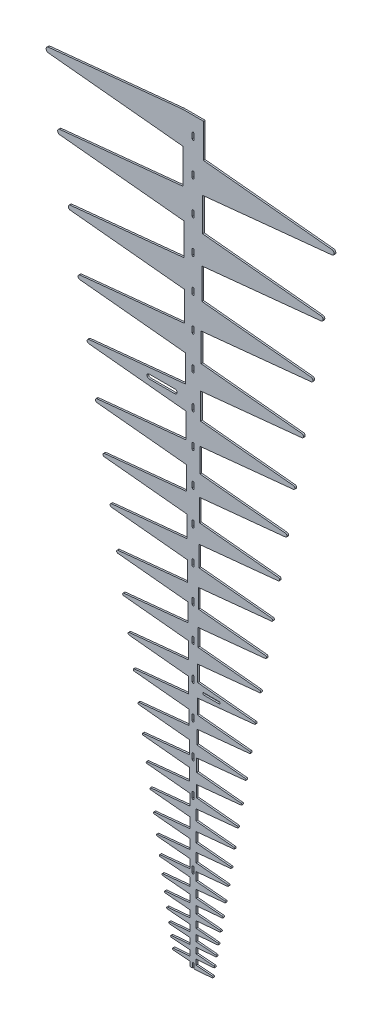
SolidWorks part; units mm, degrees
material "Copper"
ref_plane "front" through (0, 0, 0) normal (0, 0, 1) x (1, 0, 0)
ref_plane "top" through (0, 0, 0) normal (0, 1, 0) x (1, 0, 0)
ref_plane "right" through (0, 0, 0) normal (1, 0, 0) x (0, 0, -1)
ref_axis "Axis1" through (0, -2.7284, 0) along (0, 1, 0)
sketch "Sketch5" plane through (0, 0, 0) normal (0, 0, 1) x (1, 0, 0)
  line L1 (0.4572, 17.3748) -> (0.4572, 16.7446) construction
  line L2 (0.819, 67.0336) -> (11.8645, 68.1402)
  line L4 (11.8645, 68.5446) -> (0.8887, 69.6408)
  line L5 (-0.444, 34.8013) -> (-5.904, 34.2717)
  line L6 (0.4572, 34.8888) -> (6.1549, 35.4415)
  line L7 (6.155, 35.6943) -> (0.4625, 36.2508)
  line L8 (-6.4164, 37.1761) -> (-0.4818, 37.7606)
  line L9 (6.6886, 38.7197) -> (0.5018, 39.3334)
  line L10 (-6.9722, 40.3276) -> (-0.5227, 40.9717)
  line L11 (7.2676, 42.0024) -> (0.5445, 42.6782)
  line L12 (0.5445, 44.5635) -> (0.5445, 42.6782)
  line L13 (-0.5227, 42.7855) -> (-0.5227, 40.9717)
  line L14 (-0.444, 36.3394) -> (-6.4163, 36.9233)
  line L15 (-0.5227, 42.7855) -> (-7.5753, 43.4944)
  line L16 (-5.9039, 34.0189) -> (-0.4572, 33.4948)
  line L17 (0.5018, 41.074) -> (7.2675, 41.7497)
  line L18 (-0.4818, 39.431) -> (-0.4818, 37.7606)
  line L19 (0.4625, 37.8536) -> (0.4625, 36.2508)
  line L20 (-0.444, 36.3394) -> (-0.444, 34.8013)
  line L21 (0.5018, 41.074) -> (0.5018, 39.3334)
  line L22 (-0.6677, 54.647) -> (-9.6631, 55.5487)
  line L23 (-9.663, 55.9026) -> (-0.7246, 56.7938)
  line L24 (0.8887, 69.6408) -> (0.8887, 72.7352)
  line L25 (-0.853, 69.8147) -> (-0.853, 66.8661)
  line L26 (0.4625, 37.8536) -> (6.6885, 38.4669)
  line L27 (-0.4818, 39.431) -> (-6.9721, 40.0748)
  line L28 (-0.853, 69.8147) -> (-12.3433, 70.9623)
  line L29 (-12.3432, 71.4172) -> (-0.9257, 72.5545)
  line L30 (-7.5753, 43.7471) -> (-0.5671, 44.4517)
  line L31 (-0.5671, 44.4517) -> (-0.5671, 46.4176)
  line L32 (-0.5671, 46.4176) -> (-8.2061, 47.1795)
  line L33 (-8.2061, 47.4828) -> (-0.6155, 48.2385)
  line L35 (-0.6155, 48.2385) -> (-0.6155, 50.3737)
  line L36 (-0.6155, 50.3737) -> (-8.9161, 51.2055)
  line L37 (-8.9162, 51.5088) -> (-0.6677, 52.3407)
  line L38 (-0.6677, 52.3407) -> (-0.6677, 54.647)
  line L39 (0.5445, 44.5635) -> (7.8864, 45.3016)
  line L40 (7.8863, 45.5746) -> (0.5908, 46.3022)
  line L41 (0.5908, 46.3022) -> (0.5908, 48.3586)
  line L42 (0.5908, 48.3586) -> (8.5538, 49.1514)
  line L43 (8.5539, 49.4547) -> (0.6411, 50.2477)
  line L44 (0.6411, 50.2477) -> (0.6411, 52.4726)
  line L45 (0.6411, 52.4726) -> (9.2935, 53.3452)
  line L46 (9.2934, 53.6485) -> (0.6956, 54.5104)
  line L47 (0.6956, 56.9354) -> (10.0724, 57.8704)
  line L48 (10.0725, 58.2242) -> (0.7547, 59.1594)
  line L49 (0.6956, 54.5104) -> (0.6956, 56.9354)
  line L50 (-0.7246, 56.7938) -> (-0.7246, 59.3079)
  line L51 (-0.7246, 59.3079) -> (-10.499, 60.2888)
  line L52 (-10.4989, 60.6426) -> (-0.7862, 61.6131)
  line L53 (-0.7862, 61.6131) -> (-0.7862, 64.3522)
  line L54 (0.7547, 59.1594) -> (0.7547, 61.767)
  line L55 (0.7547, 61.767) -> (10.9198, 62.7827)
  line L56 (10.9197, 63.1871) -> (0.819, 64.1924)
  line L57 (0.819, 64.1924) -> (0.819, 67.0336)
  line L58 (-2.6379, 14.96) -> (-23.301, 132.1467) construction
  line L59 (-1.6146, 132.1467) -> (-0.1828, 14.96) construction
  line L60 (-0.7862, 64.3522) -> (-11.3824, 65.4068)
  line L61 (-11.3826, 65.8112) -> (-0.853, 66.8661)
  line L62 (-0.9257, 72.5545) -> (-0.9257, 75.766)
  line L63 (0.8887, 72.7352) -> (12.8662, 73.9282)
  line L64 (12.8663, 74.3832) -> (0.9641, 75.5765)
  line L65 (0.9641, 75.5765) -> (0.9641, 78.9109)
  line L66 (-0.9257, 75.766) -> (-13.4111, 77.0178)
  line L67 (-13.411, 77.4727) -> (-1.0044, 78.714)
  line L68 (-1.0044, 78.714) -> (-1.0044, 82.2104)
  line L69 (-1.0044, 82.2104) -> (-14.5463, 83.563)
  line L70 (0.9641, 78.9109) -> (13.9552, 80.2107)
  line L71 (13.9552, 80.7162) -> (1.0463, 82.0056)
  line L72 (1.0463, 82.0056) -> (1.0463, 85.636)
  line L73 (-14.5465, 84.0685) -> (-1.0897, 85.4213)
  line L74 (-1.0897, 85.4213) -> (-1.0897, 89.1922)
  line L75 (1.0463, 85.636) -> (15.1622, 87.055)
  line L76 (15.1622, 87.5605) -> (1.1353, 88.9688)
  line L77 (1.1353, 88.9688) -> (1.1353, 92.9201)
  line L78 (-1.0897, 89.1922) -> (-15.7803, 90.6672)
  line L79 (-15.7803, 91.2232) -> (-1.1824, 92.6876)
  line L80 (-1.1824, 92.6876) -> (-1.1824, 96.7798)
  line L81 (1.1353, 92.9201) -> (16.4484, 94.4562)
  line L82 (16.4484, 95.0122) -> (1.2319, 96.5378)
  line L83 (1.2319, 96.5378) -> (1.2319, 100.8239)
  line L84 (-1.1824, 96.7798) -> (-17.121, 98.3778)
  line L85 (-17.121, 98.9844) -> (-1.283, 100.5718)
  line L86 (-1.283, 100.5718) -> (-1.283, 105.013)
  line L87 (1.2319, 100.8239) -> (17.846, 102.4891)
  line L88 (17.846, 103.0957) -> (1.3366, 104.7504)
  line L89 (0, 0) -> (0, 132.1467) construction
  line L90 (1.3366, 104.7504) -> (1.3366, 109.4001)
  line L91 (1.6146, 132.1467) -> (0.1828, 14.96) construction
  line L92 (2.6379, 14.96) -> (23.301, 132.1467) construction
  line L93 (-1.283, 105.013) -> (-18.5778, 106.7464)
  line L95 (-18.5779, 107.4035) -> (-1.3922, 109.1265)
  line L96 (-1.3922, 109.1265) -> (-1.3922, 113.9465)
  line L97 (1.3366, 109.4001) -> (19.3644, 111.2074)
  line L98 (19.3645, 111.8645) -> (1.4503, 113.6614)
  line L99 (1.4503, 113.6614) -> (1.4503, 118.7058)
  line L100 (-1.3922, 113.9465) -> (-20.1606, 115.829)
  line L101 (-20.1606, 116.5367) -> (-1.5106, 118.4086)
  line L102 (-1.5106, 118.4086) -> (-1.5106, 123.64)
  line L103 (1.4503, 118.7058) -> (21.0141, 120.6695)
  line L104 (21.0141, 121.3771) -> (1.5697, 123.3306)
  line L105 (-1.5106, 123.64) -> (-21.88, 125.6864)
  line L106 (-21.8797, 126.4446) -> (-1.5697, 128.4732)
  line L107 (-0.4572, 33.4948) -> (-0.4572, 32.0694)
  line L108 (-1.5697, 128.4732) -> (1.5697, 128.4732)
  line L109 (1.5697, 128.4732) -> (1.5697, 123.3306)
  line L110 (0.4572, 34.8888) -> (0.4572, 33.4069)
  line L111 (0.4572, 33.4069) -> (5.6631, 32.906)
  line L112 (5.663, 32.6532) -> (0.4572, 32.1566)
  line L113 (0.4572, 32.1566) -> (0.4572, 30.7855)
  line L114 (-0.4572, 32.0694) -> (-5.4319, 31.595)
  line L115 (-5.4317, 31.3421) -> (-0.4572, 30.8719)
  line L116 (-0.4572, 30.8719) -> (-0.4572, 29.553)
  line L117 (0.4572, 30.7855) -> (5.2098, 30.3364)
  line L118 (5.2097, 30.0835) -> (0.4572, 29.6386)
  line L119 (0.4572, 29.6386) -> (0.4572, 28.3698)
  line L120 (-0.4572, 29.553) -> (-4.9966, 29.1281)
  line L121 (-4.9965, 28.8752) -> (-0.4572, 28.4545)
  line L122 (-0.4572, 28.4545) -> (-0.4572, 27.234)
  line L123 (-0.4572, 27.234) -> (-4.5955, 26.8546)
  line L124 (0.4572, 28.3698) -> (4.792, 27.9681)
  line L125 (4.7919, 27.7152) -> (0.4572, 27.3178)
  line L126 (0.4572, 27.3178) -> (0.4572, 26.1436)
  line L127 (-4.5954, 26.6016) -> (-0.4572, 26.2265)
  line L128 (-0.4572, 26.2265) -> (-0.4572, 25.0969)
  line L129 (-0.4572, 25.0969) -> (-4.2258, 24.7593)
  line L130 (0.4572, 26.1436) -> (4.4069, 25.7856)
  line L131 (4.4068, 25.5326) -> (0.4572, 25.1788)
  line L132 (0.4572, 25.1788) -> (0.4572, 24.0921)
  line L133 (-4.2257, 24.5063) -> (-0.4572, 24.173)
  line L134 (-0.4572, 24.173) -> (-0.4572, 23.1275)
  line L135 (0.4572, 24.0921) -> (4.0519, 23.7741)
  line L136 (4.0518, 23.5211) -> (0.4572, 23.2073)
  line L137 (0.4572, 23.2073) -> (0.4572, 22.2016)
  line L138 (-0.4572, 23.1275) -> (-3.885, 22.8283)
  line L139 (-3.8849, 22.5753) -> (-0.4572, 22.2803)
  line L140 (-0.4572, 22.2803) -> (-0.4572, 21.3127)
  line L141 (0.4572, 22.2016) -> (3.7248, 21.9203)
  line L142 (3.7246, 21.6673) -> (0.4572, 21.3902)
  line L143 (0.4572, 21.3902) -> (0.4572, 20.4594)
  line L144 (-0.4572, 21.3127) -> (-3.5709, 21.0487)
  line L145 (-3.5707, 20.7956) -> (-0.4572, 20.5357)
  line L146 (-0.4572, 20.5357) -> (-0.4572, 19.6403)
  line L147 (0.4572, 20.4594) -> (3.4232, 20.2119)
  line L148 (3.423, 19.9588) -> (0.4572, 19.7154)
  line L149 (0.4572, 19.7154) -> (0.4572, 18.8541)
  line L150 (-0.4572, 19.6403) -> (-3.2814, 19.4086)
  line L151 (-3.2812, 19.1554) -> (-0.4572, 18.9278)
  line L152 (-0.4572, 18.9278) -> (-0.4572, 18.0993)
  line L153 (0.4572, 18.8541) -> (3.1452, 18.6374)
  line L154 (3.145, 18.3842) -> (0.4572, 18.1716)
  line L155 (0.4572, 18.1716) -> (0.4572, 17.3748)
  line L156 (-0.4572, 18.0993) -> (-3.0145, 17.897)
  line L157 (-3.0143, 17.6438) -> (-0.4572, 17.4456)
  line L158 (-0.4572, 17.4456) -> (-0.4572, 16.8716)
  line L159 (0.4572, 17.3748) -> (2.8889, 17.1863)
  line L160 (2.8889, 16.9331) -> (0.4572, 16.7446)
  line L162 (-7.4216, 17.399) -> (-1.0806, 17.399) construction
  line L163 (11.7994, 111.536) -> (-7.7641, 111.536) construction
  line L164 (0.4572, 16.7446) -> (0.127, 16.7446)
  line L165 (0.127, 16.7446) -> (0.127, 17.3965)
  line L166 (-0.127, 17.3965) -> (-0.127, 16.7446)
  line L167 (-0.127, 16.7446) -> (-0.3302, 16.7446)
  arc A0 (6.1549, 35.4415) -> (6.155, 35.6943) centre (6.1426, 35.5679) ccw
  arc A1 (-6.4163, 36.9233) -> (-6.4164, 37.1761) centre (-6.4039, 37.0497) cw
  arc A2 (6.6885, 38.4669) -> (6.6886, 38.7197) centre (6.6761, 38.5933) ccw
  arc A3 (-6.9721, 40.0748) -> (-6.9722, 40.3276) centre (-6.9596, 40.2012) cw
  arc A4 (7.2675, 41.7497) -> (7.2676, 42.0024) centre (7.2549, 41.8761) ccw
  arc A5 (-9.6631, 55.5487) -> (-9.663, 55.9026) centre (-9.6454, 55.7257) cw
  arc A6 (10.0724, 57.8704) -> (10.0725, 58.2242) centre (10.0548, 58.0473) ccw
  arc A7 (10.9198, 62.7827) -> (10.9197, 63.1871) centre (10.8996, 62.9849) ccw
  arc A8 (11.8645, 68.1402) -> (11.8645, 68.5446) centre (11.8443, 68.3424) ccw
  arc A9 (-10.499, 60.2888) -> (-10.4989, 60.6426) centre (-10.4812, 60.4657) cw
  arc A10 (-11.3824, 65.4068) -> (-11.3826, 65.8112) centre (-11.3623, 65.609) cw
  arc A11 (-12.3433, 70.9623) -> (-12.3432, 71.4172) centre (-12.3205, 71.1898) cw
  arc A12 (12.8662, 73.9282) -> (12.8663, 74.3832) centre (12.8435, 74.1557) ccw
  arc A13 (-13.4111, 77.0178) -> (-13.411, 77.4727) centre (-13.3883, 77.2452) cw
  arc A14 (13.9552, 80.2107) -> (13.9552, 80.7162) centre (13.93, 80.4634) ccw
  circle A15 centre (-2.6379, 35.7196) radius 0.539 construction
  circle A16 centre (-3.8606, 58.0473) radius 0.871 construction
  arc A17 (-14.5463, 83.563) -> (-14.5465, 84.0685) centre (-14.5211, 83.8158) cw
  arc A18 (15.1622, 87.055) -> (15.1622, 87.5605) centre (15.1368, 87.3077) ccw
  arc A19 (-7.5753, 43.4944) -> (-7.5753, 43.7471) centre (-7.5626, 43.6207) cw
  arc A20 (-8.2061, 47.1795) -> (-8.2061, 47.4828) centre (-8.191, 47.3311) cw
  arc A21 (-8.9161, 51.2055) -> (-8.9162, 51.5088) centre (-8.9009, 51.3572) cw
  arc A22 (7.8864, 45.3016) -> (7.8863, 45.5746) centre (7.8727, 45.4381) ccw
  arc A23 (8.5538, 49.1514) -> (8.5539, 49.4547) centre (8.5387, 49.3031) ccw
  arc A24 (9.2935, 53.3452) -> (9.2934, 53.6485) centre (9.2782, 53.4968) ccw
  arc A25 (-15.7803, 90.6672) -> (-15.7803, 91.2232) centre (-15.7524, 90.9452) cw
  arc A26 (16.4484, 94.4562) -> (16.4484, 95.0122) centre (16.4205, 94.7342) ccw
  arc A27 (-17.121, 98.3778) -> (-17.121, 98.9844) centre (-17.0906, 98.6811) cw
  arc A28 (17.846, 102.4891) -> (17.846, 103.0957) centre (17.8156, 102.7924) ccw
  arc A29 (-18.5778, 106.7464) -> (-18.5779, 107.4035) centre (-18.5449, 107.075) cw
  arc A30 (19.3644, 111.2074) -> (19.3645, 111.8645) centre (19.3315, 111.536) ccw
  arc A31 (-20.1606, 115.829) -> (-20.1606, 116.5367) centre (-20.1251, 116.1829) cw
  arc A32 (21.0141, 120.6695) -> (21.0141, 121.3771) centre (20.9786, 121.0233) ccw
  arc A33 (-21.88, 125.6864) -> (-21.8797, 126.4446) centre (-21.8419, 126.0655) cw
  arc A34 (-5.904, 34.2717) -> (-5.9039, 34.0189) centre (-5.8918, 34.1453) ccw
  arc A35 (5.6631, 32.906) -> (5.663, 32.6532) centre (5.651, 32.7796) cw
  arc A36 (-5.4319, 31.595) -> (-5.4317, 31.3421) centre (-5.4198, 31.4685) ccw
  arc A37 (5.2098, 30.3364) -> (5.2097, 30.0835) centre (5.1979, 30.2099) cw
  arc A38 (-4.9966, 29.1281) -> (-4.9965, 28.8752) centre (-4.9848, 29.0016) ccw
  arc A39 (4.792, 27.9681) -> (4.7919, 27.7152) centre (4.7803, 27.8417) cw
  arc A40 (-4.5955, 26.8546) -> (-4.5954, 26.6016) centre (-4.5839, 26.7281) ccw
  arc A41 (4.4069, 25.7856) -> (4.4068, 25.5326) centre (4.3954, 25.6591) cw
  arc A42 (-4.2258, 24.7593) -> (-4.2257, 24.5063) centre (-4.2145, 24.6328) ccw
  arc A43 (4.0519, 23.7741) -> (4.0518, 23.5211) centre (4.0408, 23.6476) cw
  arc A44 (-3.885, 22.8283) -> (-3.8849, 22.5753) centre (-3.874, 22.7018) ccw
  arc A45 (3.7248, 21.9203) -> (3.7246, 21.6673) centre (3.7139, 21.7938) cw
  arc A46 (-3.5709, 21.0487) -> (-3.5707, 20.7956) centre (-3.5602, 20.9221) ccw
  arc A47 (3.4232, 20.2119) -> (3.423, 19.9588) centre (3.4126, 20.0853) cw
  arc A48 (-3.2814, 19.4086) -> (-3.2812, 19.1554) centre (-3.271, 19.282) ccw
  arc A49 (3.1452, 18.6374) -> (3.145, 18.3842) centre (3.135, 18.5108) cw
  arc A50 (-3.0145, 17.897) -> (-3.0143, 17.6438) centre (-3.0044, 17.7704) ccw
  arc A51 (2.8889, 17.1863) -> (2.8889, 16.9331) centre (2.8791, 17.0597) cw
  arc A52 (0.127, 17.3965) -> (-0.127, 17.3965) centre (0, 17.3965) ccw
  arc A53 (-0.3302, 16.7446) -> (-0.4572, 16.8716) centre (-0.3302, 16.8716) cw
  point P20 (0.4572, 17.0597)
  point P28 (0, 0)
  point P32 (-0.4572, 16.7446)
  point P141 (-13.6154, 77.2169)
  dimension "D10" = 93.5844
  dimension "D3" = 34.8888
  dimension "D12" = 126.0655
  dimension "D32" = 0.9144
  dimension "D34" = 0.1372
  dimension "D24" = 0.381
  dimension "D29" = 0.3556
  dimension "D43" = 0.3302
  dimension "D45" = 0.3302
  dimension "D47" = 0.3048
  dimension "D49" = 0.3048
  dimension "D51" = 0.2794
  dimension "D54" = 0.2794
  dimension "D55" = 0.254
  dimension "D57" = 0.254
  dimension "D59" = 0.254
  dimension "D61" = 0.2286
  dimension "D63" = 0.2286
  dimension "D65" = 0.3556
  dimension "D135" = 0.127
  dimension "D18" = 0.2286
  dimension "D20" = 0.2032
  dimension "D21" = 0.2032
  dimension "D22" = 0.2032
  dimension "D23" = 0.1778
  dimension "D25" = 0.1778
  dimension "D26" = 0.1778
  dimension "D27" = 0.1524
  dimension "D28" = 0.1524
  dimension "D30" = 0.1524
  dimension "D31" = 0.1524
  dimension "D36" = 0.127
  dimension "D37" = 0.127
  dimension "D38" = 0.127
  dimension "D5" = 128.4732
  dimension "D13" = 121.0233
  dimension "D14" = 0.0025
  dimension "D15" = 0.7
  dimension "D16" = 0.6544
  dimension "D17" = 10
  dimension "D19" = 17.399
  dimension "D41" = 116.1829
  dimension "D44" = 107.075
  dimension "D33" = 0.254
  dimension "D35" = 16.7446
  dimension "D42" = 111.536
  dimension "D46" = 102.7924
  dimension "D48" = 98.6811
  dimension "D50" = 94.7342
  dimension "D52" = 90.9452
  dimension "D53" = 87.3077
  dimension "D56" = 83.8158
  dimension "D58" = 80.4634
  dimension "D60" = 77.2452
  dimension "D62" = 74.1557
  dimension "D64" = 71.1898
  dimension "D67" = 68.3424
  dimension "D68" = 65.609
  dimension "D70" = 62.9849
  dimension "D72" = 60.4657
  dimension "D74" = 55.7257
  dimension "D76" = 58.0473
  dimension "D78" = 53.4968
  dimension "D80" = 51.3572
  dimension "D83" = 49.3031
  dimension "D84" = 47.3311
  dimension "D86" = 45.4381
  dimension "D88" = 43.6207
  dimension "D90" = 41.8761
  dimension "D92" = 40.2012
  dimension "D94" = 37.0497
  dimension "D96" = 38.5933
  dimension "D98" = 35.5679
  dimension "D100" = 34.1453
  dimension "D102" = 32.7796
  dimension "D104" = 31.4685
  dimension "D106" = 30.2099
  dimension "D108" = 29.0016
  dimension "D110" = 27.8417
  dimension "D112" = 26.7281
  dimension "D114" = 22.7018
  dimension "D115" = 24.6328
  dimension "D116" = 25.6591
  dimension "D117" = 23.6476
  dimension "D122" = 20.9221
  dimension "D123" = 21.7938
  dimension "D126" = 20.0853
  dimension "D128" = 19.282
  dimension "D130" = 18.5108
  dimension "D132" = 17.7704
  dimension "D134" = 17.0597
extrude "Extrude3" add sketch "Sketch5" along normal blind 0.254
sketch "Sketch6" plane through (0, 0, 0) normal (0, 0, 1) x (1, 0, 0)
  line L0 (-0.1397, 29.2227) -> (-0.1397, 30.0101)
  line L1 (0.1397, 30.0101) -> (0.1397, 29.2227)
  arc A0 (-0.1397, 30.0101) -> (0.1397, 30.0101) centre (0, 30.0101) cw
  arc A1 (0.1397, 29.2227) -> (-0.1397, 29.2227) centre (0, 29.2227) cw
  point P5 (0.1397, 29.6164)
  dimension "D2" = 0.7874
  dimension "D3" = 29.6164
  dimension "D1" = 0.2794
extrude "Fin Slot 1" cut sketch "Sketch6" along normal through all
sketch "Sketch7" plane through (0, 0, 0) normal (0, 0, 1) x (1, 0, 0)
  line L0 (-0.1397, 39.7637) -> (-0.1397, 38.9763)
  line L1 (0.1397, 38.9763) -> (0.1397, 39.7637)
  arc A0 (-0.1397, 38.9763) -> (0.1397, 38.9763) centre (0, 38.9763) ccw
  arc A1 (0.1397, 39.7637) -> (-0.1397, 39.7637) centre (0, 39.7637) ccw
  point P5 (0.1397, 39.37)
  dimension "D2" = 0.7874
  dimension "D3" = 39.37
  dimension "D1" = 0.2794
extrude "Fin Slot 2" cut sketch "Sketch7" along normal through all
pattern_linear "LPattern1" count 18 spacing 5.08 along (0, 1, 0) of "Fin Slot 2"
sketch "Sketch9" plane through (0, 0, 0) normal (0, 0, 1) x (1, 0, 0)
  line L0 (1.6129, 53.34) -> (3.9243, 53.34)
  line L1 (3.9243, 53.6448) -> (1.6129, 53.6448)
  line L2 (1.6129, 53.6448) -> (3.9243, 53.34) construction
  line L3 (-6.6548, 90.6145) -> (-2.7432, 90.6145)
  line L4 (-2.7432, 91.2495) -> (-6.6548, 91.2495)
  line L5 (-2.7432, 90.6145) -> (-6.6548, 91.2495) construction
  arc A0 (3.9243, 53.34) -> (3.9243, 53.6448) centre (3.9243, 53.4924) ccw
  arc A1 (1.6129, 53.6448) -> (1.6129, 53.34) centre (1.6129, 53.4924) ccw
  arc A2 (-2.7432, 90.6145) -> (-2.7432, 91.2495) centre (-2.7432, 90.932) ccw
  arc A3 (-6.6548, 91.2495) -> (-6.6548, 90.6145) centre (-6.6548, 90.932) ccw
  point P5 (2.7686, 53.4924)
  point P13 (-4.699, 90.932)
  dimension "D2" = 2.3114
  dimension "D6" = 3.9116
  dimension "D1" = 0.3048
  dimension "D3" = 2.7686
  dimension "D4" = 53.4924
  dimension "D5" = 0.635
  dimension "D7" = 4.699
  dimension "D8" = 90.932
extrude "Support Slots" cut sketch "Sketch9" along normal blind 2.54
sketch "Sketch8" plane through (0, 0, 0) normal (0, 0, 1) x (1, 0, 0)
  line L0 (10.4325, 33.4069) -> (0.4572, 33.4069)
  line L1 (0.4572, 33.4069) -> (0.4572, 32.3909)
  line L2 (-11.7101, 33.4948) -> (-11.7101, 3.9557)
  line L3 (-11.7101, 3.9557) -> (10.4325, 3.9557)
  line L4 (10.4325, 33.4069) -> (10.4325, 3.9557)
  line L5 (0.4572, 32.3909) -> (0.127, 32.3909)
  line L6 (-0.4572, 32.3909) -> (-0.4572, 33.4948)
  line L7 (-0.4572, 33.4948) -> (-11.7101, 33.4948)
  line L8 (-3.7821, 33.3756) -> (-0.8814, 33.3756) construction
  line L10 (0.127, 32.3909) -> (0.127, 33.1529)
  line L11 (-0.127, 33.1529) -> (-0.127, 32.3909)
  line L12 (-0.127, 32.3909) -> (-0.4572, 32.3909)
  arc A0 (0.127, 33.1529) -> (-0.127, 33.1529) centre (0, 33.1529) ccw
  dimension "D4" = 0.762
  dimension "D1" = 1.016
  dimension "D2" = 33.3756
  dimension "D3" = 0.254
extrude "EC-07 Shorten" [suppressed] cut sketch "Sketch8" along normal through all
fillet "Fillet1" [suppressed] radius 0.0254
sketch "Sketch10" [suppressed] plane through (0, 0, 0.254) normal (0, 0, 1) x (1, 0, 0)
  line L0 (0.4572, 32.3909) -> (0.1524, 32.3909) construction
  line L1 (0.127, 32.4163) -> (0.127, 33.1529) construction
  line L2 (-0.127, 33.1529) -> (-0.127, 32.4163) construction
  line L3 (-0.1524, 32.3909) -> (-0.4572, 32.3909) construction
  line L4 (0.4572, 32.3909) -> (0.1524, 32.3909)
  line L5 (0.127, 32.4163) -> (0.127, 33.1529)
  line L6 (-0.127, 33.1529) -> (-0.127, 32.4163)
  line L7 (-0.1524, 32.3909) -> (-0.4572, 32.3909)
  line L8 (0.4572, 32.3909) -> (0.4572, 33.6609)
  line L9 (0.4572, 32.3909) -> (0.4572, 34.8888) construction
  arc A0 (0.127, 32.4163) -> (0.1524, 32.3909) centre (0.1524, 32.4163) ccw construction
  arc A2 (-0.1524, 32.3909) -> (-0.127, 32.4163) centre (-0.1524, 32.4163) ccw construction
  arc A3 (0.127, 32.4163) -> (0.1524, 32.3909) centre (0.1524, 32.4163) ccw
  arc A4 (0.127, 33.1529) -> (-0.127, 33.1529) centre (0, 33.1529) ccw
  arc A5 (-0.1524, 32.3909) -> (-0.127, 32.4163) centre (-0.1524, 32.4163) ccw
  dimension "D1" = 1.27
sketch "Sketch11" [suppressed] plane through (0, 0, 0.254) normal (0, 0, 1) x (1, 0, 0)
  line L1 (-0.444, 36.3394) -> (-0.444, 34.8013) construction
  line L2 (-6.4163, 36.9233) -> (-0.444, 36.3394) construction
  line L3 (-21.88, 125.6864) -> (-1.5106, 123.64) construction
  line L4 (-1.5106, 123.64) -> (-1.5106, 118.4086) construction
  circle A0 centre (-1.2377, 35.6195) radius 0.7937
  circle A1 centre (-2.3044, 122.922) radius 0.7937
  dimension "D1" = 1.5875
  dimension "D2" = 1.5875
